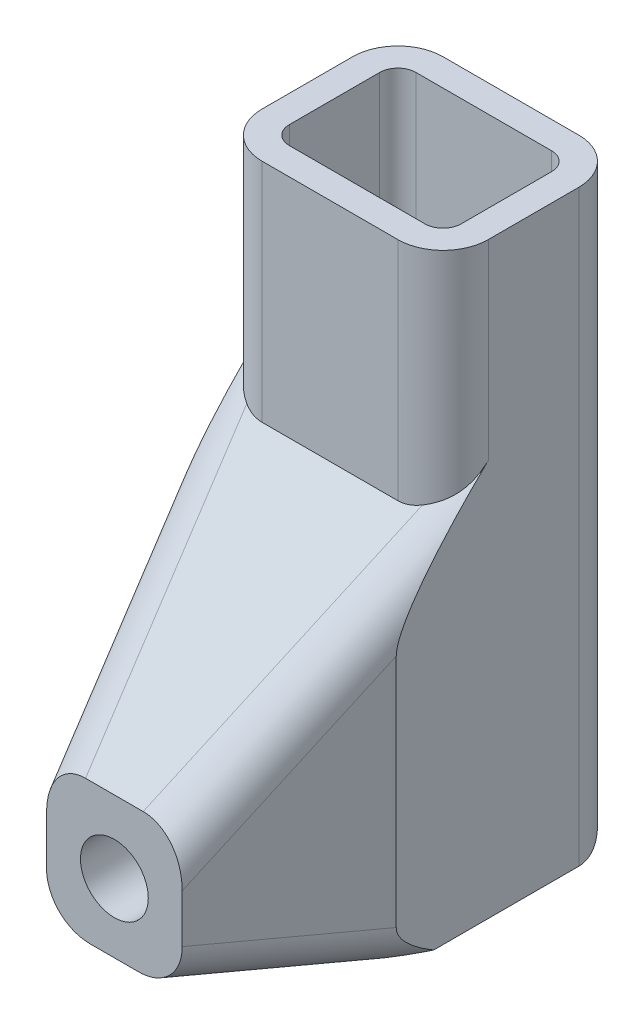
SolidWorks part; units mm, degrees
ref_plane "Front Plane" through (0, 0, 0) normal (0, 0, 1) x (1, 0, 0)
ref_plane "Top Plane" through (0, 0, 0) normal (0, 1, 0) x (1, 0, 0)
ref_plane "Right Plane" through (0, 0, 0) normal (1, 0, 0) x (0, 0, -1)
sketch "Sketch2" plane through (0, 0, 0) normal (1, 0, 0) x (0, 0, -1)
  line L0 (0, 0) -> (0, 20)
  line L1 (0, 20) -> (23.8351, 40)
  line L2 (23.8351, 40) -> (43.8351, 40)
  line L3 (43.8351, 40) -> (43.8351, 0)
  line L4 (43.8351, 0) -> (0, 0)
  dimension "D1" = 130
  dimension "D2" = 20
  dimension "D3" = 20
  dimension "D4" = 40
extrude "Boss-Extrude1" add sketch "Sketch2" along normal mid plane 25
sketch "Sketch3" plane through (0, 0, 0) normal (0, 0, 1) x (1, 0, 0)
  line L0 (0, 0) -> (0, 30.659) construction
  circle A0 centre (0, 12) radius 3.75
  point P5 (0, 0)
  dimension "D1" = 7.5
  dimension "D2" = 12
extrude "Cut-Extrude1" cut sketch "Sketch3" against normal blind 50
sketch "Sketch4" plane through (0, 0, 0) normal (0, 1, 0) x (1, 0, 0)
  line L0 (7.5, 0) -> (15, 27.9904)
  line L1 (12.5, 0) -> (-12.5, 0) construction
  line L2 (15, 27.9904) -> (20, 27.9904)
  line L3 (20, 27.9904) -> (20, -2.0096)
  line L4 (20, -2.0096) -> (-20, -2.0096)
  line L5 (-20, -2.0096) -> (-20, 27.9904)
  line L6 (-20, 27.9904) -> (-15, 27.9904)
  line L7 (-15, 27.9904) -> (-7.5, 0)
  line L8 (-7.5, 0) -> (7.5, 0)
  dimension "D1" = 15
  dimension "D2" = 7.5
  dimension "D3" = 105
  dimension "D4" = 105
  dimension "D5" = 5
  dimension "D6" = 5
  dimension "D7" = 30
  dimension "D8" = 30
  dimension "D9" = 40
extrude "Cut-Extrude2" cut sketch "Sketch4" along normal through all both and the other way through all
sketch "Sketch5" plane through (0, 0, 0) normal (1, 0, 0) x (0, 0, -1)
  line L0 (-4, 5.4705) -> (20.1481, -1)
  line L1 (20.1481, -1) -> (20.1481, -6)
  line L2 (20.1481, -6) -> (-5, -6)
  line L3 (-5, -6) -> (-5, 5.4705)
  line L4 (-5, 5.4705) -> (-4, 5.4705)
  dimension "D1" = 5
  dimension "D2" = 1
  dimension "D3" = 75
  dimension "D4" = 25
  dimension "D5" = 5
  dimension "D6" = 6
extrude "Cut-Extrude3" cut sketch "Sketch5" against normal through all both and the other way through all
sketch "Sketch6" plane through (0, 0, 0) normal (0, 1, 0) x (1, 0, 0)
  line L4 (-12.5, 43.8351) -> (-12.5, 23.8351)
  line L5 (-12.5, 23.8351) -> (12.5, 23.8351)
  line L6 (12.5, 23.8351) -> (12.5, 43.8351)
  line L7 (12.5, 43.8351) -> (-12.5, 43.8351)
  line L8 (-12.5, 43.8351) -> (-12.5, 23.8351)
  line L9 (-12.5, 23.8351) -> (12.5, 23.8351)
  line L10 (12.5, 23.8351) -> (12.5, 43.8351)
  line L11 (12.5, 43.8351) -> (-12.5, 43.8351)
  dimension "D1" = 0
extrude "Boss-Extrude2" add sketch "Sketch6" along normal blind 25 from surface starting at face at (0, 40, -33.8351)
fillet "Fillet1" radius 5 7 edges at (9.6993, 2.1993, -8.208) (10, 27.8289, -9.3301) (-10, 27.8289, -9.3301) (-9.6993, 2.1993, -8.208) (0, 0, -43.8351) (-12.5, 32.5, -43.8351) (12.5, 32.5, -43.8351)
fillet "Fillet2" radius 5 2 edges at (-12.5, 51.826, -23.8351) (12.5, 51.826, -23.8351)
sketch "Sketch7" plane through (0, 65, 0) normal (0, 1, 0) x (1, 0, 0)
  line L8 (-9.5, 38.8351) -> (-9.5, 28.8351)
  line L9 (-7.5, 26.8351) -> (7.5, 26.8351)
  line L10 (9.5, 28.8351) -> (9.5, 38.8351)
  line L11 (7.5, 40.8351) -> (-7.5, 40.8351)
  line L12 (-9.5, 38.8351) -> (-9.5, 28.8351)
  line L13 (-7.5, 26.8351) -> (7.5, 26.8351)
  line L14 (9.5, 28.8351) -> (9.5, 38.8351)
  line L15 (7.5, 40.8351) -> (-7.5, 40.8351)
  arc A8 (-9.5, 28.8351) -> (-7.5, 26.8351) centre (-7.5, 28.8351) ccw
  arc A9 (7.5, 26.8351) -> (9.5, 28.8351) centre (7.5, 28.8351) ccw
  arc A10 (9.5, 38.8351) -> (7.5, 40.8351) centre (7.5, 38.8351) ccw
  arc A11 (-7.5, 40.8351) -> (-9.5, 38.8351) centre (-7.5, 38.8351) ccw
  arc A12 (-9.5, 28.8351) -> (-7.5, 26.8351) centre (-7.5, 28.8351) ccw
  arc A13 (7.5, 26.8351) -> (9.5, 28.8351) centre (7.5, 28.8351) ccw
  arc A14 (9.5, 38.8351) -> (7.5, 40.8351) centre (7.5, 38.8351) ccw
  arc A15 (-7.5, 40.8351) -> (-9.5, 38.8351) centre (-7.5, 38.8351) ccw
  dimension "D1" = 3
extrude "Cut-Extrude4" cut sketch "Sketch7" against normal blind 25 and the other way through all
